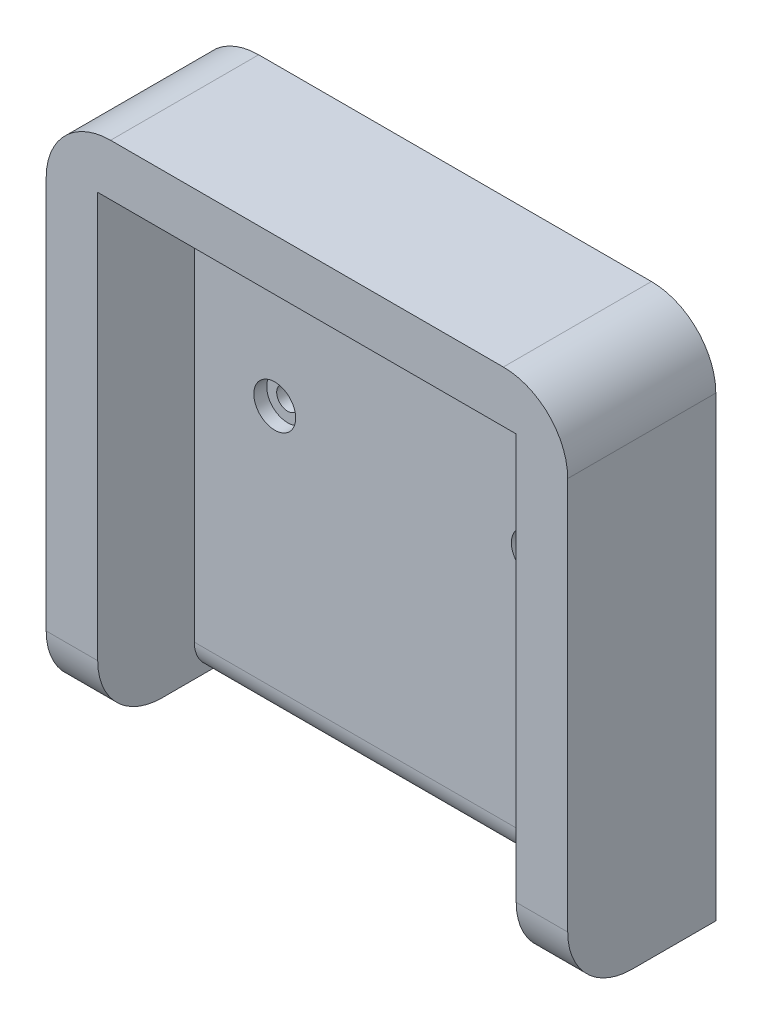
SolidWorks part; units mm, degrees
ref_plane "Plan de face" through (0, 0, 0) normal (0, 0, 1) x (1, 0, 0)
ref_plane "Plan de dessus" through (0, 0, 0) normal (0, 1, 0) x (1, 0, 0)
ref_plane "Plan de droite" through (0, 0, 0) normal (1, 0, 0) x (0, 0, -1)
sketch "Esquisse1" plane through (0, 0, 0) normal (0, 0, 1) x (1, 0, 0)
  line L1 (0, 0) -> (81, 0)
  line L2 (0, 0) -> (0, 81)
  line L3 (0, 81) -> (81, 81)
  line L4 (81, 0) -> (81, 81)
  dimension "D1" = 81
  dimension "D2" = 81
extrude "Boss.-Extru.1" add sketch "Esquisse1" along normal blind 8
sketch "Esquisse2" plane through (0, 0, 8) normal (0, 0, 1) x (1, 0, 0)
  line L1 (0, 81) -> (81, 81)
  line L3 (8, 73) -> (73, 73)
  line L4 (81, 81) -> (0, 81) construction
  line L6 (8, 73) -> (8, 0)
  line L8 (0, 81) -> (0, 0)
  line L9 (0, 0) -> (81, 0)
  line L10 (81, 0) -> (81, 81)
  line L11 (81, 81) -> (0, 81)
  line L12 (0, 81) -> (0, 0)
  line L13 (0, 0) -> (8, 0)
  line L14 (81, 0) -> (81, 81)
  line L16 (73, 73) -> (73, 0)
  line L17 (0, 0) -> (81, 0) construction
  line L19 (73, 0) -> (81, 0)
  point P9 (0, 0)
  point P12 (0, 0)
  dimension "D2" = 8
  dimension "D3" = 8
  dimension "D4" = 8
extrude "Boss.-Extru.2" add sketch "Esquisse2" along normal blind 15
fillet "Congé1" radius 10 4 edges at (0, 81, 11.5) (81, 81, 11.5) (77, 0, 23) (4, 0, 23)
fillet "Congé2" radius 5 1 edges at (40.5, 0, 8)
sketch "Esquisse4" plane through (0, 0, 8) normal (0, 0, 1) x (1, 0, 0)
  line L0 (40.5, 71.1272) -> (40.5, -7.1972) construction
  line L2 (8, 73) -> (73, 73) construction
  line L4 (8, 5) -> (73, 5) construction
  circle A0 centre (60.5, 43) radius 1.5
  circle A1 centre (20.5, 43) radius 1.5
  point P10 (40.5, 5)
  dimension "D1" = 3
  dimension "D2" = 20
  dimension "D3" = 30
hole_wizard "Chambrage pour tête cylindrique fendue M31" positions "Esquisse5" profile "Esquisse6" counterbore size "M3" standard "ISO" end condition through all
sketch "Esquisse5" plane through (0, 0, 8) normal (0, 0, 1) x (1, 0, 0)
  point P0 (20.5, 43)
  point P3 (60.5, 43)
sketch "Esquisse6" plane through (20.5, 43, 8) normal (1, 0, 0) x (0, -1, 0)
  line L0 (0, 0) -> (0, 8)
  line L1 (0, 8) -> (1.7, 8)
  line L3 (1.7, 8) -> (1.7, 2)
  line L4 (1.7, 2) -> (3.25, 2)
  line L5 (3.25, 2) -> (3.25, 0)
  line L7 (3.25, 0) -> (0, 0)
  line L11 (0, -6.35) -> (0, 107.95) construction
  dimension "Diamètre du perçage jusqu'au prochain" = 3.4
  dimension "Profondeur du perçage jusqu'au prochain" = 8
  dimension "Diamètre du chambrage" = 6.5
  dimension "Profondeur du chambrage" = 2
equation "\"epaiss_cadre\"= 8"
equation "\"D2@Esquisse1\"=\"epaiss_cadre\"*2+65"
equation "\"D1@Esquisse1\"=\"epaiss_cadre\"*2+65"
equation "\"D1@Boss.-Extru.1\"=\"epaiss_cadre\""
equation "\"D2@Esquisse2\"=\"epaiss_cadre\""
equation "\"D3@Esquisse2\"=\"epaiss_cadre\""
equation "\"D4@Esquisse2\"=\"epaiss_cadre\""
